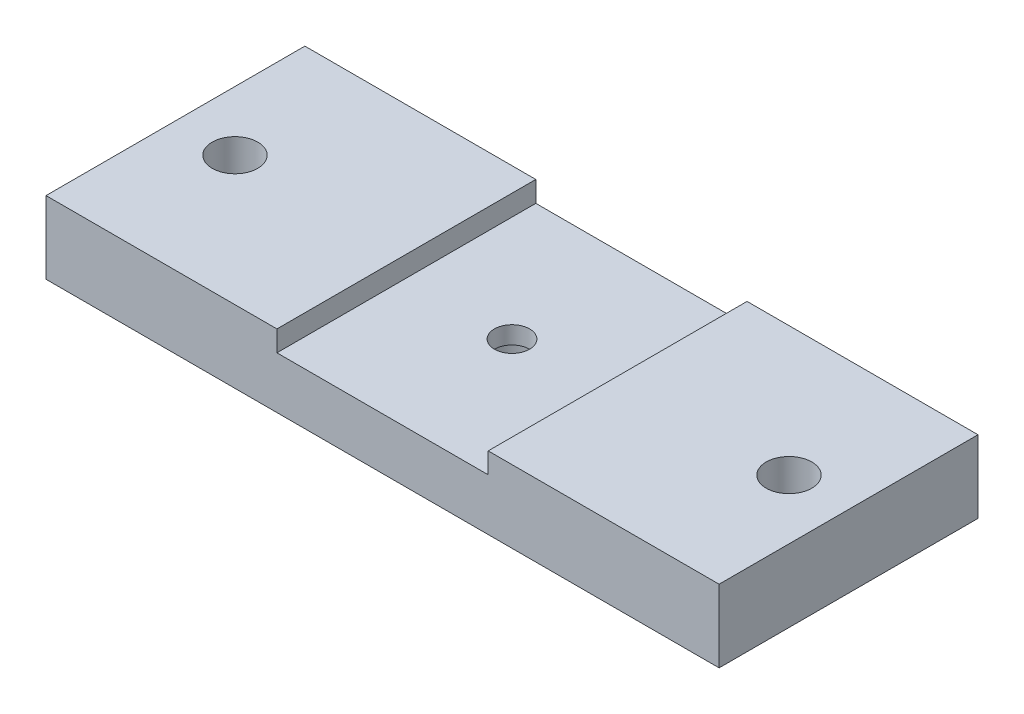
SolidWorks part; units mm, degrees
ref_plane "Front Plane" through (0, 0, 0) normal (0, 0, 1) x (1, 0, 0)
ref_plane "Top Plane" through (0, 0, 0) normal (0, 1, 0) x (1, 0, 0)
ref_plane "Right Plane" through (0, 0, 0) normal (1, 0, 0) x (0, 0, -1)
sketch "Sketch1" plane through (0, 0, 0) normal (0, 1, 0) x (1, 0, 0)
  line L1 (0, 0) -> (65, 0)
  line L2 (0, 0) -> (0, 25)
  line L3 (0, 25) -> (65, 25)
  line L4 (65, 0) -> (65, 25)
  dimension "D1" = 65
  dimension "D2" = 25
extrude "Boss-Extrude1" add sketch "Sketch1" along normal blind 7
sketch "Sketch2" plane through (0, 7, 0) normal (0, 1, 0) x (1, 0, 0)
  line L0 (65, 25) -> (0, 25) construction
  line L1 (22.3, 25) -> (42.7, 25)
  line L2 (22.3, 25) -> (22.3, 0)
  line L3 (22.3, 0) -> (42.7, 0)
  line L4 (42.7, 25) -> (42.7, 0)
  line L5 (0, 0) -> (65, 0) construction
  point P8 (32.5, 25)
  point P10 (32.5, 25)
  dimension "D1" = 20.4
extrude "Cut-Extrude1" cut sketch "Sketch2" against normal blind 2
sketch "Sketch3" plane through (0, 0, 0) normal (0, -1, 0) x (-1, 0, 0)
  line L0 (0, 25) -> (0, 0) construction
  line L1 (0, 0) -> (-65, 0) construction
  circle A0 centre (-32.5, 12.5) radius 1.7
  point P4 (0, 12.5)
  point P7 (-32.5, 0)
  dimension "D1" = 3.4
extrude "Cut-Extrude2" cut sketch "Sketch3" against normal through all
sketch "Sketch4" plane through (0, 0, 0) normal (0, -1, 0) x (-1, 0, 0)
  circle A0 centre (-32.5, 12.5) radius 3
  dimension "D1" = 6
extrude "Cut-Extrude3" cut sketch "Sketch4" against normal blind 3.3
sketch "Sketch5" plane through (0, 0, 0) normal (0, -1, 0) x (-1, 0, 0)
  line L0 (-59.25, 12.5) -> (-32.5, 12.5) construction
  line L1 (-32.5, 12.5) -> (-5.75, 12.5) construction
  circle A0 centre (-5.75, 12.5) radius 2.2
  circle A1 centre (-59.25, 12.5) radius 2.2
  dimension "D1" = 4.4
  dimension "D2" = 53.5
extrude "Cut-Extrude4" cut sketch "Sketch5" against normal through all
chamfer "Chamfer1" distance 1 angle 45 2 edges at (59.25, 0, -14.7) (5.75, 0, -14.7)
